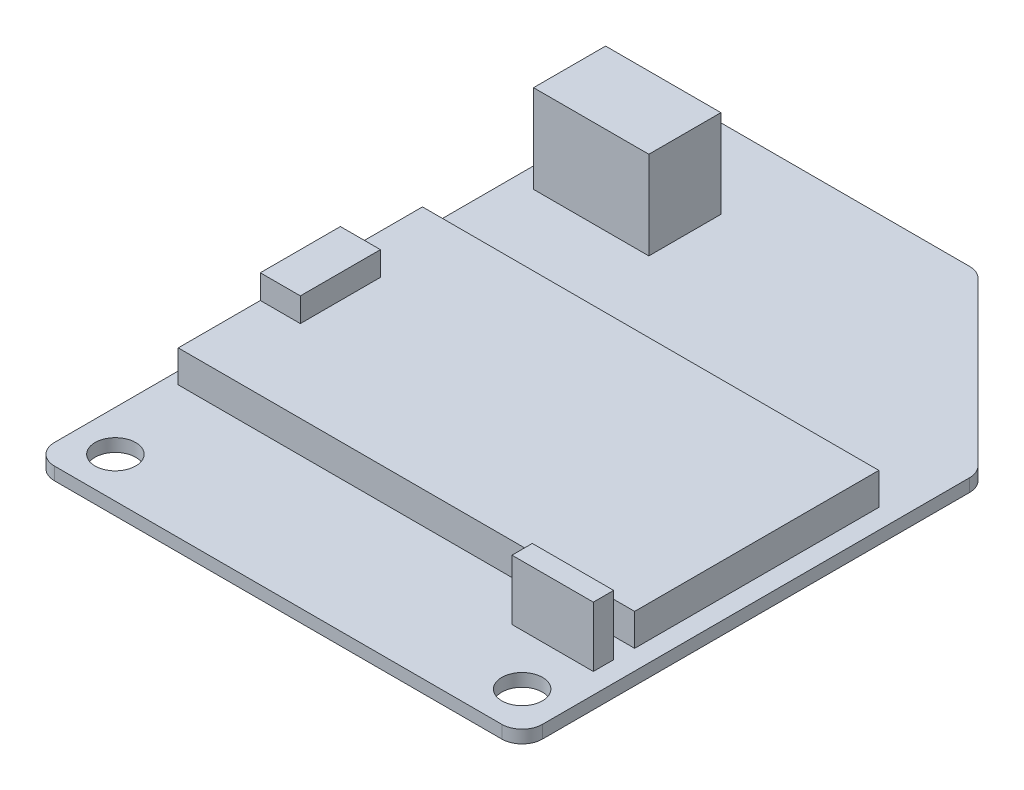
SolidWorks part; units mm, degrees
ref_plane "Front Plane" through (0, 0, 0) normal (0, 0, 1) x (1, 0, 0)
ref_plane "Top Plane" through (0, 0, 0) normal (0, 1, 0) x (1, 0, 0)
ref_plane "Right Plane" through (0, 0, 0) normal (1, 0, 0) x (0, 0, -1)
sketch "Board_Sketch" plane through (0, 0, 0) normal (0, 1, 0) x (1, 0, 0)
  line L0 (30.48, -36.83) -> (30.48, 16.51)
  line L1 (27.94, -39.37) -> (-27.94, -39.37)
  line L2 (30.48, -36.83) -> (30.48, 39.37) construction
  line L3 (30.48, 39.37) -> (-27.94, 39.37) construction
  line L4 (-30.48, -36.83) -> (-30.48, 36.83)
  line L5 (30.48, -39.37) -> (-30.48, 39.37) construction
  line L6 (30.48, 39.37) -> (-30.48, -39.37) construction
  line L7 (-27.94, 39.37) -> (7.62, 39.37)
  line L9 (7.62, 36.83) -> (7.62, 39.37) construction
  line L10 (9.4161, 38.6261) -> (7.62, 36.83) construction
  line L11 (29.7361, 18.3061) -> (27.94, 16.51) construction
  line L12 (27.94, 16.51) -> (30.48, 16.51) construction
  line L13 (9.4161, 38.6261) -> (29.7361, 18.3061)
  line L14 (-30.48, -39.37) -> (-25.4001, -34.2901) construction
  line L15 (30.48, -39.37) -> (25.4001, -34.2901) construction
  line L16 (-30.48, 39.37) -> (-25.4001, 34.2901) construction
  arc A0 (27.94, -39.37) -> (30.48, -36.83) centre (27.94, -36.83) ccw
  arc A1 (-27.94, -39.37) -> (-30.48, -36.83) centre (-27.94, -36.83) cw
  arc A2 (-27.94, 39.37) -> (-30.48, 36.83) centre (-27.94, 36.83) ccw
  arc A3 (7.62, 39.37) -> (9.4161, 38.6261) centre (7.62, 36.83) cw
  arc A4 (30.48, 16.51) -> (29.7361, 18.3061) centre (27.94, 16.51) ccw
  circle A5 centre (-25.4001, -34.2901) radius 2.54
  circle A6 centre (25.4001, -34.2901) radius 2.54
  circle A7 centre (-25.4001, 34.2901) radius 2.54
  point P0 (0, 0)
  dimension "D3" = 2.54
  dimension "D6" = 7.184
  dimension "D8" = 5.08
  dimension "D1" = 60.96
  dimension "D2" = 78.74
  dimension "D4" = 45
  dimension "D5" = 35.56
extrude "Board" add sketch "Board_Sketch" along normal blind 1.6 contours L4 A2 L7 A3 L13 A4 L0 A0 L1 A1
extrude "Board_Holes" cut sketch "BoardSketch<3>" along normal up to surface (1.6 mm away) contours A7 | A5 | A6 up to face at (1.8559, 1.6, -3.6339)
sketch "BoardSketch<3>" plane through (0, 0, 0) normal (0, 1, 0) x (1, 0, 0) same geometry as "Board_Sketch"
sketch "Port_Sketch" plane through (0, 1.6, 0) normal (0, 1, 0) x (1, 0, 0)
  line L0 (-30.48, -36.83) -> (-30.48, 36.83) construction
  line L1 (-28.98, 7.64) -> (28.02, 7.64)
  line L2 (-28.98, 7.64) -> (-28.98, -22.86)
  line L3 (-28.98, -22.86) -> (28.02, -22.86)
  line L4 (28.02, 7.64) -> (28.02, -22.86)
  line L5 (27.94, -39.37) -> (-27.94, -39.37) construction
  line L11 (-27.937, 29.47) -> (-27.937, 39.37) construction
  line L12 (-27.937, 29.47) -> (-13.537, 29.47)
  line L13 (-27.937, 29.47) -> (-27.937, 20.47)
  line L14 (-27.937, 20.47) -> (-13.537, 20.47)
  line L15 (-13.537, 29.47) -> (-13.537, 20.47)
  line L16 (-27.94, 39.37) -> (7.62, 39.37) construction
  line L17 (30.48, -36.83) -> (30.48, 16.51) construction
  line L18 (17.78, -25.4) -> (27.94, -25.4)
  line L19 (17.78, -25.4) -> (17.78, -27.94)
  line L20 (17.78, -27.94) -> (27.94, -27.94)
  line L21 (27.94, -25.4) -> (27.94, -27.94)
  dimension "D1" = 1.5
  dimension "D2" = 16.51
  dimension "D3" = 57
  dimension "D4" = 30.5
  dimension "D7" = 14.4
  dimension "D8" = 9
  dimension "D9" = 9.9
  dimension "D10" = 2.543
  dimension "D11" = 10.16
  dimension "D12" = 2.54
  dimension "D13" = 2.54
  dimension "D14" = 11.43
extrude "Barrel_Conn" add sketch "Port_Sketch" along normal blind 11 contours L14 L15 L12 L13
sketch "Barrel_Sketch" plane through (-27.937, 0, 0) normal (-1, 0, 0) x (0, 0, 1)
  line L0 (-24.97, 1.6) -> (-24.97, 8.1) construction
  line L1 (-29.47, 1.6) -> (-20.47, 1.6) construction
  circle A0 centre (-24.97, 8.1) radius 3.25
  dimension "D2" = 6.5
  dimension "D1" = 6.5
extrude "Barrel_Conn_Hole" cut sketch "Barrel_Sketch" against normal blind 9
extrude "Pin_Header" add sketch "PortSketch<3>" along normal blind 7.5 contours L18 L21 L20 L19
sketch "PortSketch<3>" plane through (0, 1.6, 0) normal (0, 1, 0) x (1, 0, 0) same geometry as "Port_Sketch"
extrude "ESP8266" add sketch "PortSketch<4>" along normal blind 4 contours L3 L4 L1 L2
sketch "PortSketch<4>" plane through (0, 1.6, 0) normal (0, 1, 0) x (1, 0, 0) same geometry as "Port_Sketch"
sketch "USB_Sketch" plane through (0, 5.6, 0) normal (0, 1, 0) x (1, 0, 0)
  line L1 (-28.98, -2.61) -> (-23.98, -2.61)
  line L2 (-28.98, -2.61) -> (-28.98, -12.61)
  line L3 (-28.98, -12.61) -> (-23.98, -12.61)
  line L4 (-23.98, -2.61) -> (-23.98, -12.61)
  line L7 (-28.98, 7.64) -> (-28.98, -22.86) construction
  line L8 (-23.98, -7.61) -> (-28.98, -7.61) construction
  line L9 (-28.98, 7.64) -> (-28.98, -22.86) construction
  dimension "D1" = 10
  dimension "D2" = 5
extrude "USB_Port" add sketch "USB_Sketch" along normal blind 3
sketch "LM7805_Sketch" plane through (0, 0, 0) normal (0, -1, 0) x (1, 0, 0)
  line L0 (30.48, 36.83) -> (30.48, -16.51) construction
  line L1 (-4.005, 0.08) -> (0.635, 0.08)
  line L2 (-4.005, 0.08) -> (-4.005, -10.16)
  line L3 (-4.005, -10.16) -> (0.635, -10.16)
  line L4 (0.635, 0.08) -> (0.635, -10.16)
  line L5 (-27.94, -39.37) -> (7.62, -39.37) construction
  dimension "D1" = 10.24
  dimension "D2" = 4.64
  dimension "D3" = 29.845
  dimension "D4" = 29.21
extrude "LM7805_TH" add sketch "LM7805_Sketch" along normal blind 9.07
